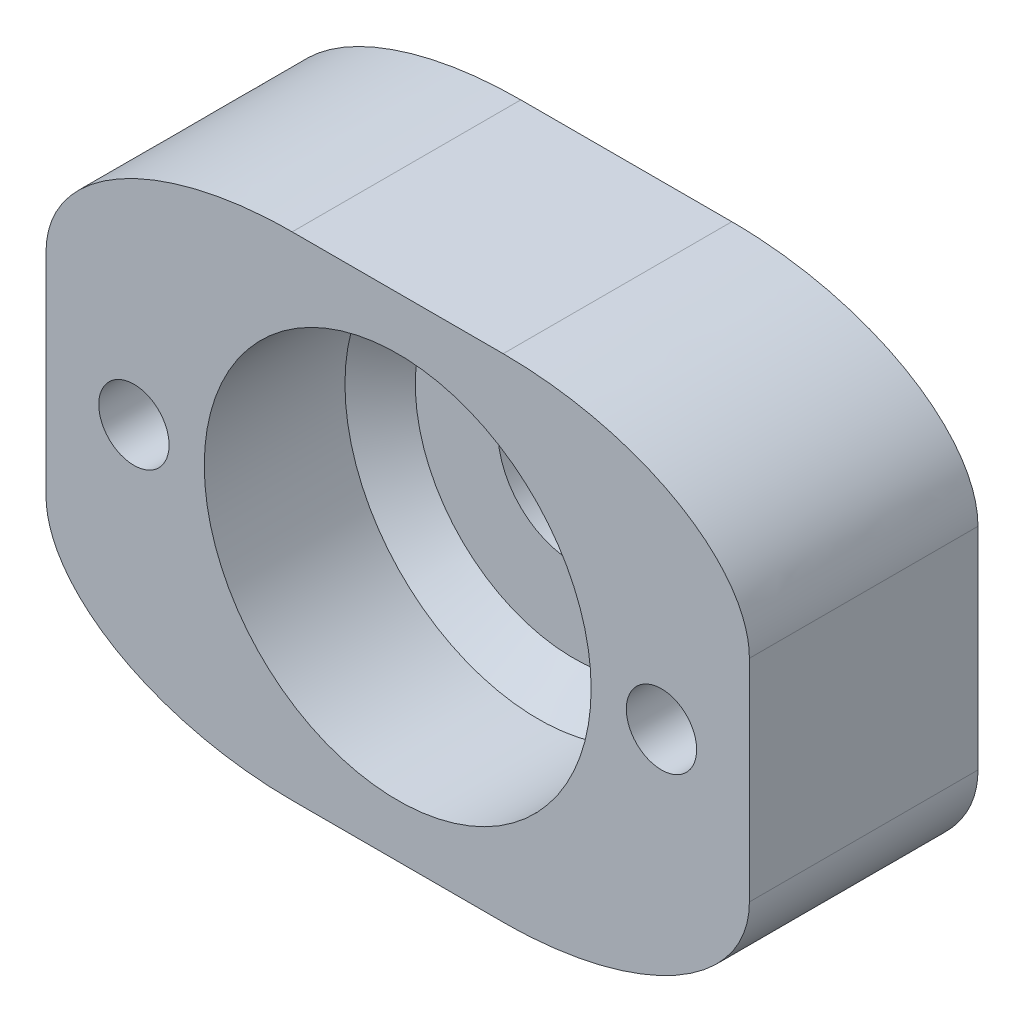
SolidWorks part; units mm, degrees
material "ABS"
ref_plane "Płaszczyzna przednia" through (0, 0, 0) normal (0, 0, 1) x (1, 0, 0)
ref_plane "Płaszczyzna górna" through (0, 0, 0) normal (0, 1, 0) x (1, 0, 0)
ref_plane "Płaszczyzna prawa" through (0, 0, 0) normal (1, 0, 0) x (0, 0, -1)
sketch "Szkic1" plane through (0, 0, 0) normal (0, 0, 1) x (1, 0, 0)
  line L1 (-20, -14) -> (20, -14)
  line L2 (-20, -14) -> (-20, 14)
  line L3 (-20, 14) -> (20, 14)
  line L4 (20, -14) -> (20, 14)
  line L5 (-20, -14) -> (20, 14) construction
  line L6 (-20, 14) -> (20, -14) construction
  circle A0 centre (0, 0) radius 11
  dimension "D1" = 40
  dimension "D2" = 28
extrude "Dodanie-wyciągnięcie1" add sketch "Szkic1" along normal blind 10
sketch "Szkic2" plane through (0, 0, 0) normal (0, 0, -1) x (-1, 0, 0)
  line L0 (20, -14) -> (-20, -14) construction
  line L1 (20, 14) -> (20, -14) construction
  line L2 (-20, -14) -> (-20, 14) construction
  line L3 (-20, 14) -> (20, 14) construction
  line L4 (20, -14) -> (-20, -14)
  line L5 (20, 14) -> (20, -14)
  line L6 (-20, -14) -> (-20, 14)
  line L7 (-20, 14) -> (20, 14)
extrude "Dodanie-wyciągnięcie2" add sketch "Szkic2" along normal blind 3
chamfer "Sfazowanie1" distance 2 angle 45 1 edges at (11, 0, 0)
sketch "Szkic3" plane through (0, 0, 0) normal (0, 0, 1) x (1, 0, 0)
  circle A0 centre (0, 0) radius 4.3
  dimension "D1" = 8.6
extrude "Wytnij-wyciągnięcie1" cut sketch "Szkic3" against normal blind 3
sketch "Szkic4" plane through (0, 0, 10) normal (0, 0, 1) x (1, 0, 0)
  line L0 (-20, 14) -> (-20, -14) construction
  line L1 (20, -14) -> (20, 14) construction
  line L2 (-20, -14) -> (20, -14) construction
  circle A0 centre (-15, 0) radius 2
  circle A1 centre (15, 0) radius 2
  point P4 (0, 0)
  dimension "D1" = 4
  dimension "D2" = 5
  dimension "D3" = 5
  dimension "D4" = 14
extrude "Wytnij-wyciągnięcie2" cut sketch "Szkic4" against normal blind 6
fillet "Zaokrąglenie1" radius 14 2 edges at (20, -14, 3.5) (-20, 14, 3.5)
fillet "Zaokrąglenie2" radius 14 2 edges at (20, 14, 3.5) (-20, -14, 3.5)
sketch "Szkic5" plane through (0, 0, -3) normal (0, 0, -1) x (-1, 0, 0)
  circle A0 centre (-15, 0) radius 2 construction
  circle A1 centre (15, 0) radius 2 construction
  circle A2 centre (-15, 0) radius 2 construction
  circle A3 centre (15, 0) radius 2 construction
  circle A4 centre (-15, 0) radius 2.6
  circle A5 centre (15, 0) radius 2.6
  dimension "D1" = 5.2
extrude "Wytnij-wyciągnięcie3" cut sketch "Szkic5" against normal blind 7
